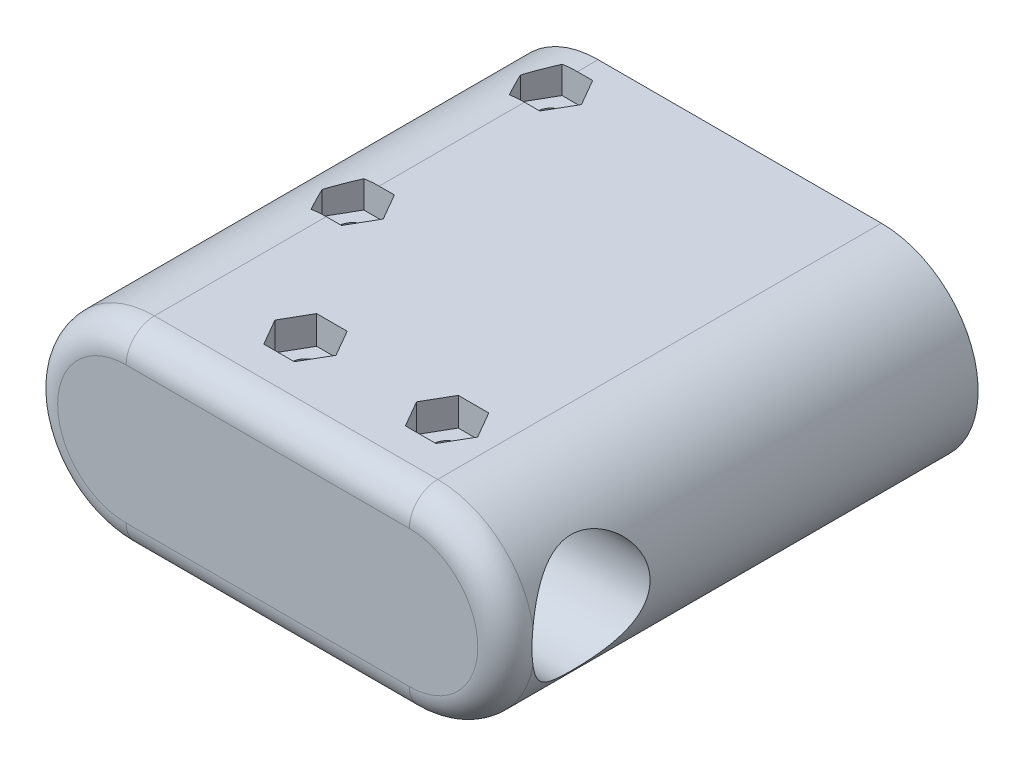
SolidWorks part; units mm, degrees
ref_plane "Front Plane" through (0, 0, 0) normal (0, 0, 1) x (1, 0, 0)
ref_plane "Top Plane" through (0, 0, 0) normal (0, 1, 0) x (1, 0, 0)
ref_plane "Right Plane" through (0, 0, 0) normal (1, 0, 0) x (0, 0, -1)
sketch "Sketch1" plane through (0, 0, 0) normal (0, 0, 1) x (1, 0, 0)
  line L0 (-73.6221, 11.8383) -> (106.3779, 11.8383)
  line L1 (-73.6221, -8.6617) -> (106.3779, -8.6617)
  line L2 (16.3779, 11.8383) -> (16.3779, -8.6617) construction
  circle A0 centre (-73.6221, 1.5883) radius 6.25
  circle A1 centre (-43.6221, 1.5883) radius 4.25
  arc A2 (-73.6221, 11.8383) -> (-73.6221, -8.6617) centre (-73.6221, 1.5883) ccw
  arc A3 (106.3779, 11.8383) -> (106.3779, -8.6617) centre (106.3779, 1.5883) cw
  circle A4 centre (76.3779, 1.5883) radius 4.25
  circle A5 centre (106.3779, 1.5883) radius 6.25
  dimension "D1" = 8.5
  dimension "D2" = 12.5
  dimension "D5" = 4
  dimension "D3" = 30
  dimension "D4" = 90
extrude "Boss-Extrude1" add sketch "Sketch1" along normal blind 50
sketch "Sketch2" plane through (0, 0, 50) normal (0, 0, 1) x (1, 0, 0)
  line L0 (106.3779, 11.8383) -> (-73.6221, 11.8383) construction
  line L1 (-73.6221, -8.6617) -> (106.3779, -8.6617) construction
  line L2 (-43.6221, 11.8383) -> (132.2063, 11.8383)
  line L3 (132.2063, 11.8383) -> (132.2063, -8.6617)
  line L4 (132.2063, -8.6617) -> (-43.6221, -8.6617)
  arc A0 (-43.6221, 11.8383) -> (-43.6221, -8.6617) centre (-43.6221, 1.5883) cw
extrude "Cut-Extrude1" cut sketch "Sketch2" against normal blind 127
sketch "Sketch3" plane through (0, 0, 50) normal (0, 0, 1) x (1, 0, 0)
  line L2 (-43.6221, 11.8383) -> (-73.6221, 11.8383)
  line L3 (-73.6221, -8.6617) -> (-43.6221, -8.6617)
  line L4 (-43.6221, 11.8383) -> (-73.6221, 11.8383)
  line L5 (-73.6221, -8.6617) -> (-43.6221, -8.6617)
  arc A2 (-43.6221, -8.6617) -> (-43.6221, 11.8383) centre (-43.6221, 1.5883) ccw
  arc A3 (-73.6221, 11.8383) -> (-73.6221, -8.6617) centre (-73.6221, 1.5883) ccw
  arc A4 (-43.6221, -8.6617) -> (-43.6221, 11.8383) centre (-43.6221, 1.5883) ccw
  arc A5 (-73.6221, 11.8383) -> (-73.6221, -8.6617) centre (-73.6221, 1.5883) ccw
  dimension "D1" = 0
extrude "Boss-Extrude2" add sketch "Sketch3" against normal blind 20
ref_plane "Plane1" through (-43.6221, 0, 0) normal (-1, 0, 0) x (0, 0, 1)
sketch "Sketch4" plane through (-43.6221, 0, 0) normal (-1, 0, 0) x (0, 0, 1)
  line L0 (41, 11.8383) -> (41, -8.6617) construction
  line L1 (50, 11.8383) -> (0, 11.8383) construction
  line L2 (0, -8.6617) -> (50, -8.6617) construction
  line L3 (50, -8.6617) -> (50, 11.8383) construction
  circle A0 centre (41, 1.5883) radius 6.25
  dimension "D1" = 12.5
  dimension "D2" = 9
extrude "Cut-Extrude2" cut sketch "Sketch4" against normal blind 20
sketch "Sketch5" plane through (-43.6221, 0, 0) normal (1, 0, 0) x (0, 0, -1)
  circle A0 centre (-41, 1.5883) radius 6.25
  dimension "D1" = 12.5
extrude "Cut-Extrude3" cut sketch "Sketch5" against normal blind 30
fillet "Fillet1" radius 3 4 edges at (-58.6221, 11.8383, 50) (-83.8721, 1.5883, 50) (-58.6221, -8.6617, 50) (-33.3721, 1.5883, 50)
sketch "Sketch6" plane through (0, 0, 30) normal (0, 0, -1) x (-1, 0, 0)
  circle A0 centre (73.6221, 1.5883) radius 4.5
  dimension "D1" = 9
extrude "Boss-Extrude3" add sketch "Sketch6" along normal blind 30
sketch "Sketch7" plane through (0, 11.8383, 0) normal (0, 1, 0) x (1, 0, 0)
  line L0 (-73.6221, -41) -> (-46.7331, -41) construction
  line L1 (-73.6221, -47) -> (-73.6221, 0) construction
  line L2 (-73.6221, -41) -> (-73.6221, 0) construction
  line L3 (-73.6221, -47) -> (-43.6221, -47) construction
  line L4 (-43.6221, 11.275) -> (-43.6221, -11.275) construction
  line L5 (-73.6221, 0) -> (-83.8721, 0) construction
  circle A0 centre (-48.6221, -41) radius 1.5
  circle A1 centre (-63.6221, -41) radius 1.5
  circle A2 centre (-73.6221, -26) radius 1.5
  circle A3 centre (-73.6221, -5) radius 1.5
  dimension "D2" = 3
  dimension "D1" = 6
  dimension "D3" = 5
  dimension "D4" = 5
  dimension "D5" = 15
  dimension "D6" = 10
extrude "Cut-Extrude4" cut sketch "Sketch7" against normal blind 30
sketch "Sketch8" plane through (0, -8.6617, 0) normal (0, -1, 0) x (-1, 0, 0)
  line L1 (73.6221, -8.1754) -> (76.3721, -6.5877)
  line L2 (76.3721, -6.5877) -> (76.3721, -3.4123)
  line L3 (76.3721, -3.4123) -> (73.6221, -1.8246)
  line L4 (73.6221, -1.8246) -> (70.8721, -3.4123)
  line L5 (70.8721, -3.4123) -> (70.8721, -6.5877)
  line L6 (70.8721, -6.5877) -> (73.6221, -8.1754)
  line L7 (73.6221, -29.1754) -> (76.3721, -27.5877)
  line L8 (76.3721, -27.5877) -> (76.3721, -24.4123)
  line L9 (76.3721, -24.4123) -> (73.6221, -22.8246)
  line L10 (73.6221, -22.8246) -> (70.8721, -24.4123)
  line L11 (70.8721, -24.4123) -> (70.8721, -27.5877)
  line L12 (70.8721, -27.5877) -> (73.6221, -29.1754)
  line L13 (63.6221, -44.1754) -> (66.3721, -42.5877)
  line L14 (66.3721, -42.5877) -> (66.3721, -39.4123)
  line L15 (66.3721, -39.4123) -> (63.6221, -37.8246)
  line L16 (63.6221, -37.8246) -> (60.8721, -39.4123)
  line L17 (60.8721, -39.4123) -> (60.8721, -42.5877)
  line L18 (60.8721, -42.5877) -> (63.6221, -44.1754)
  line L19 (48.6221, -44.1754) -> (51.3721, -42.5877)
  line L20 (51.3721, -42.5877) -> (51.3721, -39.4123)
  line L21 (51.3721, -39.4123) -> (48.6221, -37.8246)
  line L22 (48.6221, -37.8246) -> (45.8721, -39.4123)
  line L23 (45.8721, -39.4123) -> (45.8721, -42.5877)
  line L24 (45.8721, -42.5877) -> (48.6221, -44.1754)
  circle A0 centre (73.6221, -5) radius 2.75 construction
  circle A1 centre (73.6221, -26) radius 2.75 construction
  circle A2 centre (63.6221, -41) radius 2.75 construction
  circle A3 centre (48.6221, -41) radius 2.75 construction
  dimension "D1" = 5.5
sketch "Sketch9" plane through (0, 11.8383, 0) normal (0, 1, 0) x (1, 0, 0)
  line L1 (-60.3889, -41) -> (-62.0055, -38.2)
  line L2 (-62.0055, -38.2) -> (-65.2387, -38.2)
  line L3 (-65.2387, -38.2) -> (-66.8552, -41)
  line L4 (-66.8552, -41) -> (-65.2387, -43.8)
  line L5 (-65.2387, -43.8) -> (-62.0055, -43.8)
  line L6 (-62.0055, -43.8) -> (-60.3889, -41)
  line L7 (-45.3889, -41) -> (-47.0055, -38.2)
  line L8 (-47.0055, -38.2) -> (-50.2387, -38.2)
  line L9 (-50.2387, -38.2) -> (-51.8552, -41)
  line L10 (-51.8552, -41) -> (-50.2387, -43.8)
  line L11 (-50.2387, -43.8) -> (-47.0055, -43.8)
  line L12 (-47.0055, -43.8) -> (-45.3889, -41)
  line L13 (-70.3889, -26) -> (-72.0055, -23.2)
  line L14 (-72.0055, -23.2) -> (-75.2387, -23.2)
  line L15 (-75.2387, -23.2) -> (-76.8552, -26)
  line L16 (-76.8552, -26) -> (-75.2387, -28.8)
  line L17 (-75.2387, -28.8) -> (-72.0055, -28.8)
  line L18 (-72.0055, -28.8) -> (-70.3889, -26)
  line L19 (-70.3889, -5) -> (-72.0055, -2.2)
  line L20 (-72.0055, -2.2) -> (-75.2387, -2.2)
  line L21 (-75.2387, -2.2) -> (-76.8552, -5)
  line L22 (-76.8552, -5) -> (-75.2387, -7.8)
  line L23 (-75.2387, -7.8) -> (-72.0055, -7.8)
  line L24 (-72.0055, -7.8) -> (-70.3889, -5)
  circle A0 centre (-63.6221, -41) radius 2.8 construction
  circle A1 centre (-48.6221, -41) radius 2.8 construction
  circle A2 centre (-73.6221, -26) radius 2.8 construction
  circle A3 centre (-73.6221, -5) radius 2.8 construction
  dimension "D1" = 5.6
  dimension "D2" = 5.6
  dimension "D3" = 5.6
  dimension "D4" = 5.6
extrude "Cut-Extrude5" cut sketch "Sketch9" against normal blind 3
